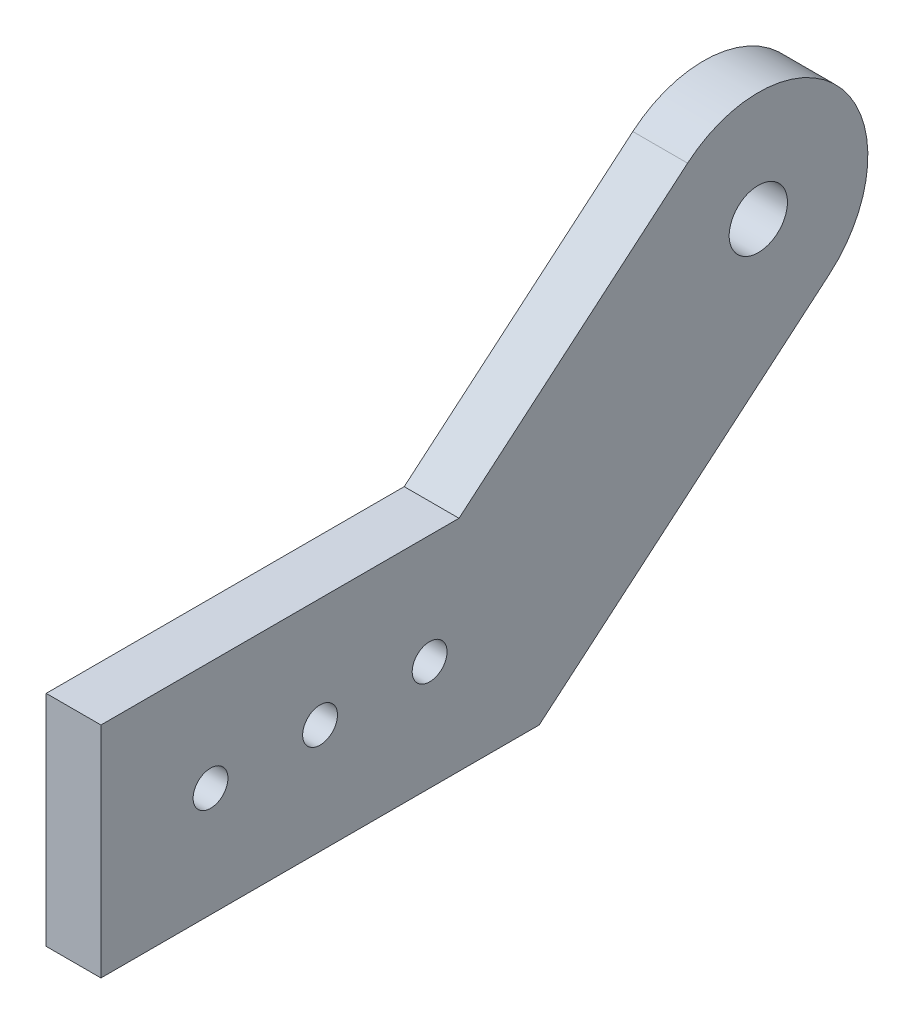
SolidWorks part; units mm, degrees
material "6061-T6 (SS)"
ref_plane "Front" through (0, 0, 0) normal (0, 0, 1) x (1, 0, 0)
ref_plane "Top" through (0, 0, 0) normal (0, 1, 0) x (1, 0, 0)
ref_plane "Right" through (0, 0, 0) normal (1, 0, 0) x (0, 0, -1)
sketch "Sketch1" plane through (0, 0, 0) normal (1, 0, 0) x (0, 0, -1)
  line L0 (50.8, 0) -> (84.3986, 28.4009)
  line L1 (0, 0) -> (50.8, 0)
  line L2 (0, 0) -> (0, 25.4)
  line L3 (0, 25.4) -> (41.503, 25.4)
  line L5 (68.0014, 47.7991) -> (41.503, 25.4)
  arc A0 (84.3986, 28.4009) -> (68.0014, 47.7991) centre (76.2, 38.1) ccw
  dimension "D3" = 76.2
  dimension "D1" = 25.4
  dimension "D2" = 25.4
  dimension "D4" = 50.8
  dimension "D5" = 38.1
extrude "Boss-Extrude1" add sketch "Sketch1" along normal blind 6.35
hole_wizard "#10-32 Tapped Hole1" positions "Sketch2" profile "Sketch3" tap size "#10-32" standard "ANSI Inch" end condition through all
sketch "Sketch2" plane through (6.35, 0, 0) normal (1, 0, 0) x (0, 0, -1)
  line L0 (0, 0) -> (12.7, 12.7) construction
  line L1 (12.7, 12.7) -> (25.4, 12.7) construction
  line L2 (25.4, 12.7) -> (38.1, 12.7) construction
  line L3 (38.1, 12.7) -> (50.8, 25.4) construction
  line L4 (41.503, 25.4) -> (0, 25.4) construction
  line L6 (0, 25.4) -> (0, 0) construction
  point P0 (12.7, 12.7)
  point P2 (25.4, 12.7)
  point P4 (38.1, 12.7)
  dimension "D1" = 50.8
  dimension "D2" = 12.7
sketch "Sketch3" plane through (6.35, 12.7, -12.7) normal (0, 1, 0) x (0, 0, -1)
  line L0 (0, 0) -> (0, 6.35)
  line L1 (0, 6.35) -> (2.0193, 6.35)
  line L2 (2.0193, 6.35) -> (2.0193, 0)
  line L5 (2.0193, 0) -> (0, 0)
  line L11 (0, -6.35) -> (0, 107.95) construction
  dimension "Thru Tap Drill Dia." = 4.0386
  dimension "Thru Tap Drill Depth" = 6.35
cosmetic thread "Hole Thread1" parameters "D2"=4.826
cosmetic thread "Hole Thread2" parameters "D2"=4.826
cosmetic thread "Hole Thread3" parameters "D2"=4.826
hole_wizard "1/4 Clearance Hole1" positions "Sketch4" profile "Sketch5" hole size "1/4" standard "ANSI Inch" end condition through all
sketch "Sketch4" plane through (6.35, 0, 0) normal (1, 0, 0) x (0, 0, -1)
  arc A0 (84.3986, 28.4009) -> (68.0014, 47.7991) centre (76.2, 38.1) ccw construction
  point P0 (76.2, 38.1)
sketch "Sketch5" plane through (6.35, 38.1, -76.2) normal (0, 1, 0) x (0, 0, -1)
  line L0 (0, 0) -> (0, 6.35)
  line L1 (0, 6.35) -> (3.3782, 6.35)
  line L2 (3.3782, 6.35) -> (3.3782, 0)
  line L5 (3.3782, 0) -> (0, 0)
  line L11 (0, -6.35) -> (0, 107.95) construction
  dimension "Thru Hole Dia." = 6.7564
  dimension "Thru Hole Depth" = 6.35
